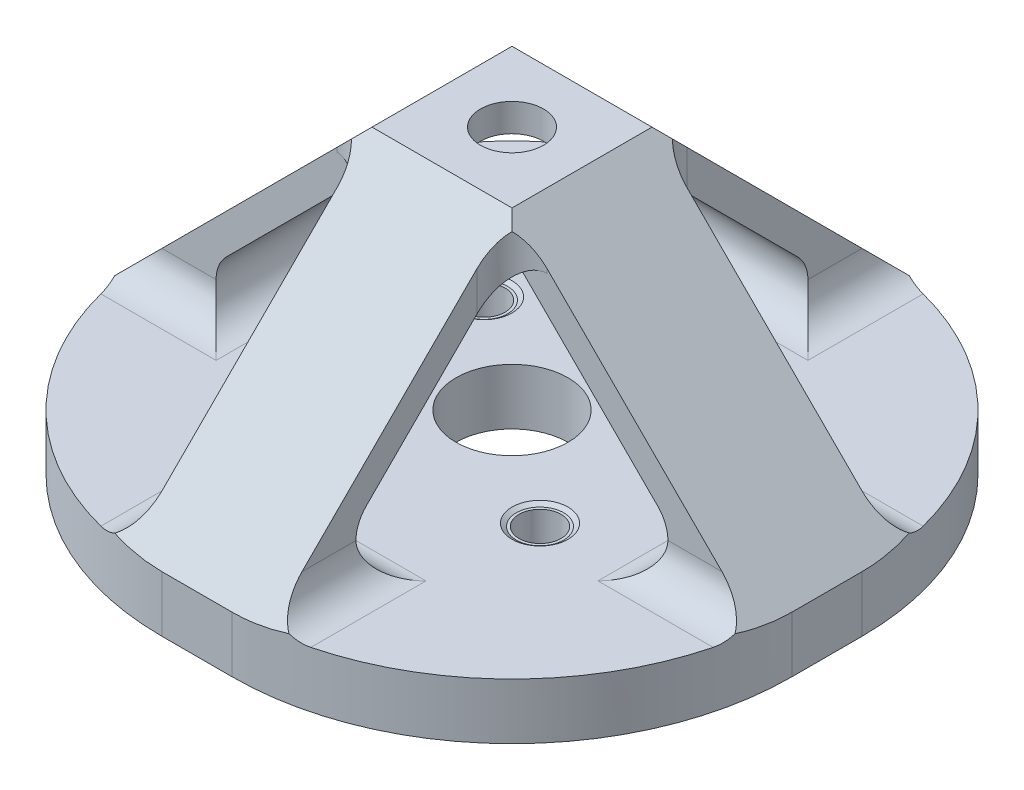
SolidWorks part; units mm, degrees
ref_plane "Front Plane" through (0, 0, 0) normal (0, 0, 1) x (1, 0, 0)
ref_plane "Top Plane" through (0, 0, 0) normal (0, 1, 0) x (1, 0, 0)
ref_plane "Right Plane" through (0, 0, 0) normal (1, 0, 0) x (0, 0, -1)
sketch "Sketch1" plane through (0, 0, 0) normal (0, 1, 0) x (1, 0, 0)
  line L1 (22.5, -22.5) -> (-22.5, -22.5)
  line L2 (22.5, -22.5) -> (22.5, 22.5)
  line L3 (22.5, 22.5) -> (-22.5, 22.5)
  line L4 (-22.5, -22.5) -> (-22.5, 22.5)
  line L5 (22.5, -22.5) -> (-22.5, 22.5) construction
  line L6 (22.5, 22.5) -> (-22.5, -22.5) construction
  point P0 (0, 0)
  dimension "D1" = 45
  dimension "D2" = 45
extrude "Boss-Extrude1" add sketch "Sketch1" along normal blind 4
sketch "Sketch2" plane through (0, 4, 0) normal (0, 1, 0) x (1, 0, 0)
  circle A0 centre (-8, 6) radius 1.5
  circle A1 centre (8, 6) radius 1.5
  circle A2 centre (8, -6) radius 1.5
  circle A3 centre (-8, -6) radius 1.5
  dimension "D1" = 3
  dimension "D2" = 3
  dimension "D3" = 3
  dimension "D4" = 3
  dimension "D5" = 16
  dimension "D6" = 8
  dimension "D7" = 6
  dimension "D8" = 6
extrude "Cut-Extrude1" cut sketch "Sketch2" against normal blind 4
sketch "Sketch3" plane through (0, 4, 0) normal (0, 1, 0) x (1, 0, 0)
  circle A0 centre (-8, 6) radius 2
  circle A1 centre (8, 6) radius 2
  circle A2 centre (8, -6) radius 2
  circle A3 centre (-8, -6) radius 2
  dimension "D1" = 4
  dimension "D2" = 4
  dimension "D3" = 4
  dimension "D4" = 4
extrude "Cut-Extrude2" cut sketch "Sketch3" against normal blind 0.2
chamfer "Chamfer1" distance 0.2 angle 57 4 edges at (-8, 3.8, -4) (8, 3.8, -4) (8, 3.8, 8) (-8, 3.8, 8)
sketch "Sketch5" plane through (0, 0, 0) normal (0, 0, 1) x (1, 0, 0)
  line L0 (-22.5, 4) -> (0, 26.5)
  line L1 (22.5, 4) -> (0, 26.5)
  line L2 (-22.5, 4) -> (22.5, 4) construction
  line L3 (-5, 21.5) -> (5, 21.5)
  line L4 (-21.0858, 2.5858) -> (0, 23.6716)
  line L5 (21.0858, 2.5858) -> (0, 23.6716)
  line L6 (-5, 19.5) -> (5, 19.5)
  line L7 (-22.5, 4) -> (-21.0858, 2.5858)
  line L8 (22.5, 4) -> (21.0858, 2.5858)
  dimension "D1" = 45
  dimension "D2" = 45
  dimension "D4" = 7
  dimension "D3" = 2
extrude "Boss-Extrude2" add sketch "Sketch5" along normal mid plane 10
sketch "Sketch6" plane through (0, 0, 0) normal (1, 0, 0) x (0, 0, -1)
  line L0 (-22.5, 4) -> (-0.0182, 26.5182)
  line L1 (-0.0182, 26.5182) -> (22.5, 4)
  line L2 (5, 4) -> (22.5, 4) construction
  line L3 (-22.5, 4) -> (-5, 4) construction
  line L4 (-5, 21.5) -> (5, 21.5)
  line L5 (-21.0846, 2.5869) -> (-0.017, 23.6886)
  line L6 (-0.017, 23.6886) -> (21.0858, 2.5858)
  line L7 (-5, 19.5) -> (5, 19.5)
  line L8 (-22.5, 4) -> (-21.0846, 2.5869)
  line L10 (21.0858, 2.5858) -> (22.5, 4)
  line L11 (-5, 21.5) -> (-22.5, 4)
  line L12 (-21.0846, 2.5869) -> (-22.5, 4)
  line L13 (-21.0846, 2.5869) -> (-2.2021, 21.5)
  line L14 (-2.2021, 21.5) -> (-5, 21.5)
  line L15 (2.1716, 21.5) -> (21.0858, 2.5858)
  line L16 (21.0858, 2.5858) -> (22.5, 4)
  line L17 (22.5, 4) -> (5, 21.5)
  line L18 (5, 21.5) -> (2.1716, 21.5)
  point P20 (3.0503, 21.5)
  dimension "D1" = 45
  dimension "D2" = 45.046
  dimension "D3" = 2
extrude "Boss-Extrude3" add sketch "Sketch6" along normal mid plane 10
sketch "Sketch7" plane through (0, 21.5, 0) normal (0, 1, 0) x (1, 0, 0)
  circle A0 centre (0, 0) radius 2.25
  dimension "D1" = 4.5
extrude "Cut-Extrude3" cut sketch "Sketch7" against normal blind 32
sketch "Sketch8" plane through (0, 0, 0) normal (0, -1, 0) x (1, 0, 0)
  circle A0 centre (0, 0) radius 4
  dimension "D1" = 8
extrude "Cut-Extrude4" cut sketch "Sketch8" against normal blind 10
fillet "Fillet1" radius 2.5 20 edges at (-5, 20.0988, 5) (5, 20.0988, 5) (4.1716, 19.5, 0.0136) (-4.1716, 19.5, 0.0136) (0, 4, 19.6739) (-5, 4, 21.0869) (0, 19.5, 4.1989) (5, 4, 21.0869) (-5, 20.0858, -5) (5, 20.0858, -5) (0, 19.5, -4.1716) (0, 4, -19.6716) (5, 4, -21.0858) (-5, 4, -21.0858) (21.0858, 4, -5) (19.6716, 4, 0) (21.0858, 4, 5) (-21.0858, 4, -5) (-19.6716, 4, 0) (-21.0858, 4, 5)
fillet "Fillet2" radius 20 4 edges at (22.5, 2, 22.5) (22.5, 2, -22.5) (-22.5, 2, -22.5) (-22.5, 2, 22.5)
